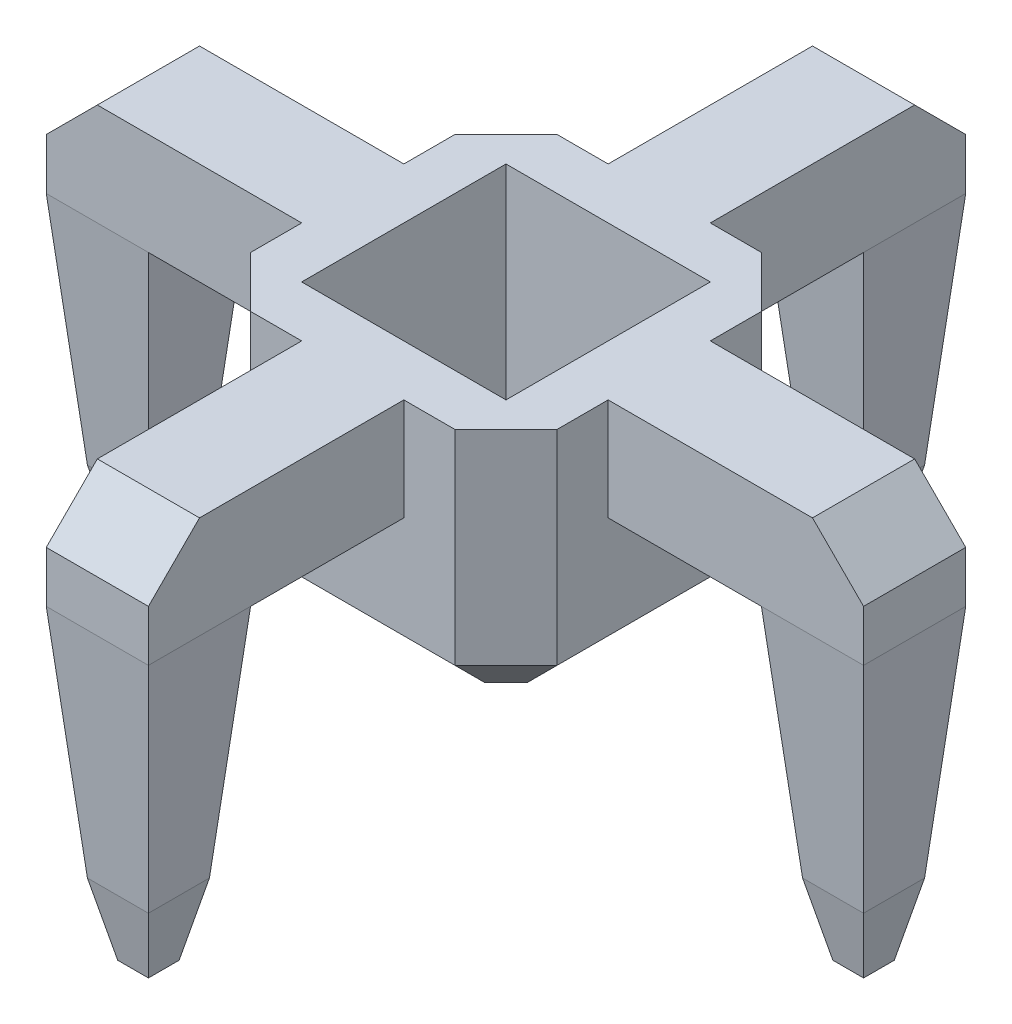
SolidWorks part; units mm, degrees
ref_plane "Front Plane" through (0, 0, 0) normal (0, 0, 1) x (1, 0, 0)
ref_plane "Top Plane" through (0, 0, 0) normal (0, 1, 0) x (1, 0, 0)
ref_plane "Right Plane" through (0, 0, 0) normal (1, 0, 0) x (0, 0, -1)
sketch "Sketch1" plane through (0, 0, 0) normal (0, 1, 0) x (1, 0, 0)
  line L1 (-15, 15) -> (15, 15)
  line L2 (-15, 15) -> (-15, -15)
  line L3 (-15, -15) -> (15, -15)
  line L4 (15, 15) -> (15, -15)
  line L5 (-15, 15) -> (15, -15) construction
  line L6 (-15, -15) -> (15, 15) construction
  point P0 (0, 0)
  dimension "D1" = 30
extrude "center" add sketch "Sketch1" against normal blind 25
sketch "Sketch2" plane through (0, 0, 0) normal (0, 1, 0) x (1, 0, 0)
  line L1 (-10, 10) -> (10, 10)
  line L2 (-10, 10) -> (-10, -10)
  line L3 (-10, -10) -> (10, -10)
  line L4 (10, 10) -> (10, -10)
  line L5 (-10, 10) -> (10, -10) construction
  line L6 (-10, -10) -> (10, 10) construction
  point P0 (0, 0)
  dimension "D1" = 20
  dimension "D2" = 20
extrude "center hole" cut sketch "Sketch2" against normal blind 20
sketch "Sketch3" plane through (0, 0, 0) normal (0, 1, 0) x (1, 0, 0)
  line L0 (15, -15) -> (15, 15) construction
  line L1 (15, 5) -> (40, 5)
  line L2 (15, 5) -> (15, -5)
  line L3 (15, -5) -> (40, -5)
  line L4 (40, 5) -> (40, -5)
  point P6 (15, 0)
  point P8 (15, 0)
  dimension "D1" = 40
  dimension "D2" = 10
extrude "arm" add sketch "Sketch3" against normal blind 10
sketch "Sketch5" plane through (0, -20, 0) normal (0, 1, 0) x (1, 0, 0)
  circle A0 centre (0, 0) radius 2.5
  dimension "D1" = 5
extrude "screw hole" cut sketch "Sketch5" against normal through all
sketch "Sketch7" plane through (0, -10, 0) normal (0, -1, 0) x (1, 0, 0)
  line L0 (15, 5) -> (40, 5) construction
  line L1 (40, -5) -> (30, -5)
  line L2 (40, -5) -> (40, 5)
  line L3 (40, 5) -> (30, 5)
  line L4 (30, -5) -> (30, 5)
  dimension "D1" = 10
extrude "leg" add sketch "Sketch7" along normal blind 30 draft 5
pattern_circular "CirPattern1" count 4 over 360 about axis through (0, 0, 0) along (0, 1, 0) of "arm", "leg"
chamfer "Chamfer1" distance 5 angle 45 4 edges at (-15, -12.5, 15) (-15, -12.5, -15) (15, -12.5, -15) (15, -12.5, 15)
chamfer "Chamfer2" distance 5 angle 45 4 edges at (40, 0, 0) (0, 0, -40) (-40, 0, 0) (0, 0, 40)
chamfer "Chamfer3" distance 5 angle 45 8 edges at (12.5, -25, -12.5) (15, -25, 0) (12.5, -25, 12.5) (0, -25, 15) (-12.5, -25, 12.5) (0, -25, -15) (-12.5, -25, -12.5) (-15, -25, 0)
chamfer "Chamfer4" distance 7 angle 7 16 edges at (35, -40, -2.3753) (32.6247, -40, 0) (35, -40, 2.3753) (37.3753, -40, 0) (2.3753, -40, 35) (0, -40, 32.6247) (-2.3753, -40, 35) (0, -40, 37.3753) (-35, -40, 2.3753) (-32.6247, -40, 0) (-35, -40, -2.3753) (-37.3753, -40, 0) (-2.3753, -40, -35) (0, -40, -32.6247) (2.3753, -40, -35) (0, -40, -37.3753)
